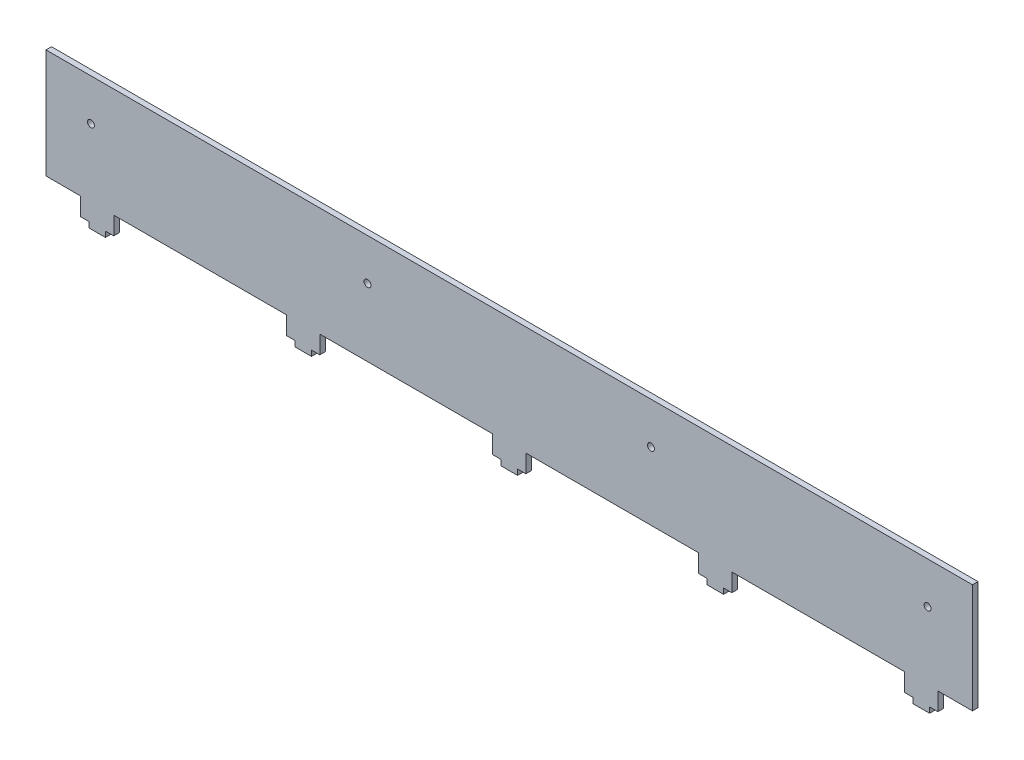
SolidWorks part; units mm, degrees
ref_plane "Спереди" through (0, 0, 0) normal (0, 0, 1) x (1, 0, 0)
ref_plane "Сверху" through (0, 0, 0) normal (0, 1, 0) x (1, 0, 0)
ref_plane "Справа" through (0, 0, 0) normal (1, 0, 0) x (0, 0, -1)
sketch "Эскиз1" plane through (0, 0, 0) normal (0, 0, 1) x (1, 0, 0)
  line L1 (-335, -46) -> (335, -46)
  line L2 (-335, -46) -> (-335, 46)
  line L3 (-335, 46) -> (335, 46)
  line L4 (335, -46) -> (335, 46)
  line L5 (0, 46) -> (0, -46) construction
  line L6 (-335, 0) -> (335, 0) construction
  point P0 (0, 0)
  dimension "D1" = 92
  dimension "D2" = 670
extrude "Бобышка-Вытянуть1" add sketch "Эскиз1" along normal mid plane 4
sketch "Эскиз2" plane through (0, 0, 2) normal (0, 0, 1) x (1, 0, 0)
  line L0 (-335, -46) -> (335, -46) construction
  line L9 (-435, -33) -> (-310, -33)
  line L10 (-435, -33) -> (-435, -46)
  line L11 (-435, -46) -> (-310, -46)
  line L12 (-310, -33) -> (-310, -46)
  line L13 (335, 46) -> (-335, 46) construction
  line L14 (-286, -33) -> (-161, -33)
  line L15 (-286, -33) -> (-286, -46)
  line L16 (-286, -46) -> (-161, -46)
  line L17 (-161, -33) -> (-161, -46)
  line L18 (-137, -33) -> (-12, -33)
  line L19 (-137, -33) -> (-137, -46)
  line L20 (-137, -46) -> (-12, -46)
  line L21 (-12, -33) -> (-12, -46)
  line L22 (12, -33) -> (137, -33)
  line L23 (12, -33) -> (12, -46)
  line L24 (12, -46) -> (137, -46)
  line L25 (137, -33) -> (137, -46)
  line L26 (161, -33) -> (286, -33)
  line L27 (161, -33) -> (161, -46)
  line L28 (161, -46) -> (286, -46)
  line L29 (286, -33) -> (286, -46)
  line L30 (310, -33) -> (435, -33)
  line L31 (310, -33) -> (310, -46)
  line L32 (310, -46) -> (435, -46)
  line L33 (435, -33) -> (435, -46)
  point P25 (-137, -39.5)
  point P26 (137, -39.5)
  dimension "D6" = 125
  dimension "D3" = 125
  dimension "D4" = 125
  dimension "D9" = 125
  dimension "D11" = 125
  dimension "D5" = 24
  dimension "D2" = 24
  dimension "D7" = 24
  dimension "D8" = 24
  dimension "D10" = 24
  dimension "D12" = 125
  dimension "D13" = 12
  dimension "D14" = 79
extrude "Вырез-Вытянуть1" cut sketch "Эскиз2" against normal through all
sketch "Эскиз3" [suppressed] plane through (0, 0, 2) normal (0, 0, 1) x (1, 0, 0)
  line L0 (-328, 8) -> (-328, -4)
  line L1 (-328, -4) -> (-318, -4)
  line L2 (-318, -4) -> (-318, -18)
  line L3 (-318, -18) -> (318, -18)
  line L4 (318, -18) -> (318, -4)
  line L5 (318, -4) -> (328, -4)
  line L6 (328, -4) -> (328, 8)
  line L7 (328, 8) -> (290, 8)
  line L8 (290, 8) -> (280, 34)
  line L9 (280, 34) -> (240, 34)
  line L10 (240, 34) -> (230, 8)
  line L11 (230, 8) -> (-230, 8)
  line L12 (-230, 8) -> (-240, 34)
  line L13 (-240, 34) -> (-280, 34)
  line L14 (-280, 34) -> (-290, 8)
  line L15 (-290, 8) -> (-328, 8)
  line L16 (0, 0) -> (0, 91.1092) construction
  line L17 (-260, 34) -> (-260, 12.7826) construction
  line L18 (260, 34) -> (260, 0) construction
  line L19 (-12, -33) -> (-137, -33) construction
  line L20 (-335, 46) -> (-335, -33) construction
  line L21 (335, 46) -> (-335, 46) construction
  dimension "D1" = 15
  dimension "D2" = 14
  dimension "D3" = 12
  dimension "D4" = 60
  dimension "D5" = 38
  dimension "D6" = 7
  dimension "D7" = 17
  dimension "D8" = 12
  dimension "D9" = 40
extrude "Вырез-Вытянуть2" [suppressed] cut sketch "Эскиз3" against normal through all
fillet "Скругление1" [suppressed] radius 10
fillet "Скругление6" [suppressed] radius 2
sketch "Эскиз4" [suppressed] plane through (0, 0, 2) normal (0, 0, 1) x (1, 0, 0)
  circle A1 centre (-302.5, -29) radius 2.5
  circle A2 centre (-302.5, -29) radius 2.5
  circle A3 centre (0, -29) radius 2.5
  circle A4 centre (0, -29) radius 2.5
  circle A5 centre (302.5, -29) radius 2.5
  circle A6 centre (302.5, -29) radius 2.5
  circle A7 centre (-102.5, 16) radius 2.5
  circle A8 centre (-102.5, 16) radius 2.5
  circle A9 centre (102.5, 16) radius 2.5
  circle A10 centre (102.5, 16) radius 2.5
  circle A11 centre (-302.5, 16) radius 2.5
  circle A12 centre (-302.5, 16) radius 2.5
  circle A13 centre (302.5, 16) radius 2.5
  circle A14 centre (302.5, 16) radius 2.5
  dimension "D1" = 0
  dimension "D2" = 0
  dimension "D3" = 0
  dimension "D4" = 0
  dimension "D5" = 0
  dimension "D6" = 0
  dimension "D7" = 0
extrude "Вырез-Вытянуть3" [suppressed] cut sketch "Эскиз4" against normal through all
sketch "Эскиз5" plane through (0, 0, 2) normal (0, 0, 1) x (1, 0, 0)
  circle A7 centre (-102.5, 16) radius 2.5
  circle A8 centre (-102.5, 16) radius 2.5
  circle A9 centre (102.5, 16) radius 2.5
  circle A10 centre (102.5, 16) radius 2.5
  circle A11 centre (-302.5, 16) radius 2.5
  circle A12 centre (-302.5, 16) radius 2.5
  circle A13 centre (302.5, 16) radius 2.5
  circle A14 centre (302.5, 16) radius 2.5
  dimension "D4" = 0
  dimension "D5" = 0
  dimension "D6" = 0
  dimension "D7" = 0
extrude "Вырез-Вытянуть4" cut sketch "Эскиз5" against normal through all
sketch "Эскиз6" plane through (0, -46, 0) normal (0, -1, 0) x (1, 0, 0)
  line L0 (286, -2) -> (310, -2) construction
  line L2 (310, 2) -> (286, 2) construction
  line L4 (161, 2) -> (137, 2) construction
  line L6 (137, -2) -> (161, -2) construction
  line L8 (-12, -2) -> (12, -2) construction
  line L10 (12, 2) -> (-12, 2) construction
  line L12 (-161, -2) -> (-137, -2) construction
  line L14 (-137, 2) -> (-161, 2) construction
  line L16 (-310, -2) -> (-286, -2) construction
  line L18 (-286, 2) -> (-310, 2) construction
  line L20 (292, -2) -> (304, -2)
  line L21 (304, -2) -> (304, 2)
  line L22 (304, 2) -> (292, 2)
  line L23 (292, 2) -> (292, -2)
  line L24 (155, 2) -> (143, 2)
  line L25 (143, 2) -> (143, -2)
  line L26 (143, -2) -> (155, -2)
  line L27 (155, -2) -> (155, 2)
  line L28 (-6, -2) -> (6, -2)
  line L29 (6, -2) -> (6, 2)
  line L30 (6, 2) -> (-6, 2)
  line L31 (-6, 2) -> (-6, -2)
  line L32 (-155, -2) -> (-143, -2)
  line L33 (-143, -2) -> (-143, 2)
  line L34 (-143, 2) -> (-155, 2)
  line L35 (-155, 2) -> (-155, -2)
  line L36 (-304, -2) -> (-292, -2)
  line L37 (-292, -2) -> (-292, 2)
  line L38 (-292, 2) -> (-304, 2)
  line L39 (-304, 2) -> (-304, -2)
  line L40 (298, 2) -> (298, -2) construction
  line L41 (286, 2) -> (310, 2) construction
  line L42 (149, 2) -> (149, -2) construction
  line L43 (137, 2) -> (161, 2) construction
  line L44 (0, 2) -> (0, -2) construction
  line L45 (-12, 2) -> (12, 2) construction
  line L46 (-149, 2) -> (-149, -2) construction
  line L47 (-161, 2) -> (-137, 2) construction
  line L48 (-298, 2) -> (-298, -2) construction
  line L49 (-310, 2) -> (-286, 2) construction
  point P62 (-292, 0)
  dimension "D1" = 12
  dimension "D2" = 12
  dimension "D3" = 12
  dimension "D4" = 12
  dimension "D5" = 12
extrude "Бобышка-Вытянуть2" add sketch "Эскиз6" along normal blind 4
equation "\"D3@Эскиз2\"=\"D6@Эскиз2\""
equation "\"D4@Эскиз2\"=\"D6@Эскиз2\""
equation "\"D9@Эскиз2\"=\"D6@Эскиз2\""
equation "\"D2@Эскиз2\"=\"D5@Эскиз2\""
equation "\"D7@Эскиз2\"=\"D5@Эскиз2\""
equation "\"D10@Эскиз2\"=\"D5@Эскиз2\""
equation "\"D12@Эскиз2\"=\"D6@Эскиз2\""
equation "\"D13@Эскиз2\"=\"D5@Эскиз2\"/2"
